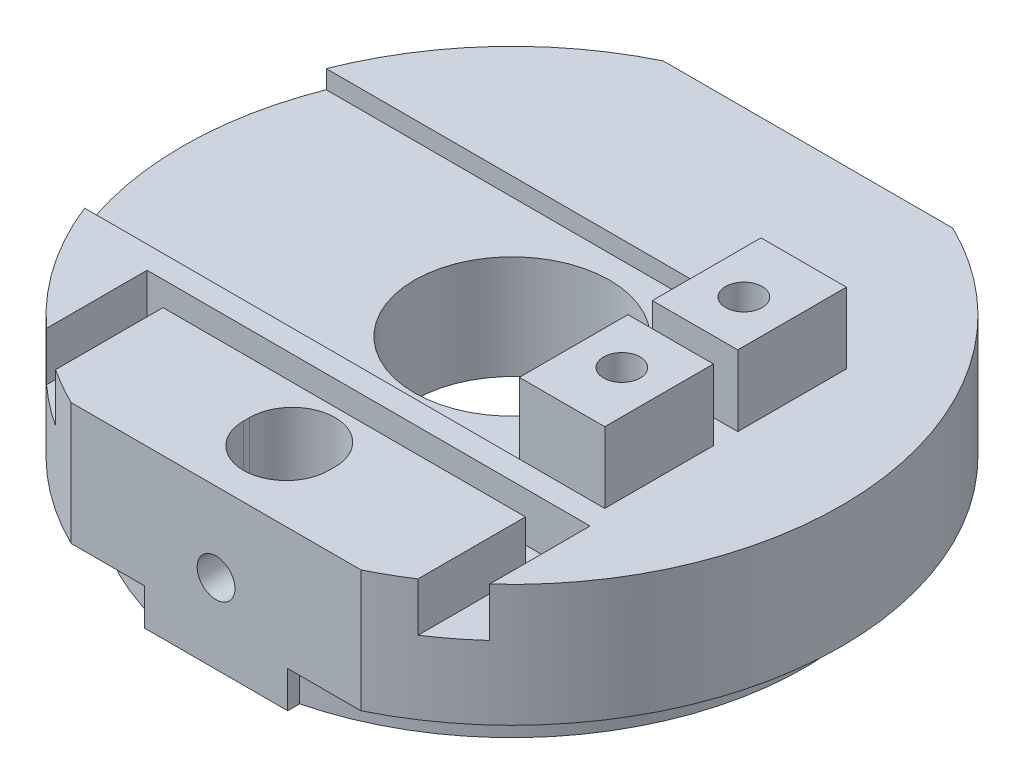
SolidWorks part; units mm, degrees
ref_plane "Front Plane" through (0, 0, 0) normal (0, 0, 1) x (1, 0, 0)
ref_plane "Top Plane" through (0, 0, 0) normal (0, 1, 0) x (1, 0, 0)
ref_plane "Right Plane" through (0, 0, 0) normal (1, 0, 0) x (0, 0, -1)
sketch "Sketch1" plane through (0, 0, 0) normal (0, 1, 0) x (1, 0, 0)
  line L0 (0, -18) -> (0, -18.5) construction
  line L5 (3.5, -18) -> (3.5, -18.5)
  line L6 (-3.5, -18) -> (-3.5, -18.5)
  line L7 (0, -14.5) -> (0, -8) construction
  line L8 (0, 27) -> (0, 24) construction
  line L9 (-17.5, -27) -> (17.5, -27)
  line L10 (-17.5, -27) -> (-17.5, -24.25)
  line L11 (-17.5, -24.25) -> (17.5, -24.25)
  line L12 (17.5, -27) -> (17.5, -24.25)
  line L13 (5.8745, -24.25) -> (-5.8745, -24.25)
  line L14 (5.8745, -24.25) -> (5.8745, -23.2699)
  line L15 (5.8745, -23.2699) -> (-5.8745, -23.2699)
  line L16 (-5.8745, -24.25) -> (-5.8745, -23.2699)
  line L18 (17.5, 27) -> (-17.5, 27)
  line L19 (17.5, 27) -> (17.5, 24.25)
  line L20 (17.5, 24.25) -> (-17.5, 24.25)
  line L21 (-17.5, 27) -> (-17.5, 24.25)
  circle A0 centre (0, 0) radius 8
  circle A1 centre (0, 0) radius 27
  circle A2 centre (0, 0) radius 24
  circle A3 centre (0, 0) radius 22
  arc A4 (3.5, -18) -> (-3.5, -18) centre (0, -18) ccw
  arc A5 (-3.5, -18.5) -> (3.5, -18.5) centre (0, -18.5) ccw
  circle A6 centre (0, 0) radius 20.75 construction
  circle A7 centre (0, 0) radius 14.5 construction
  point P12 (0, -18.25)
  point P17 (0, -14.5)
  point P18 (0, -22)
  point P23 (0, -27)
  point P24 (0, -23.2699)
  point P35 (24.3506, 24)
  dimension "D1" = 16
  dimension "D2" = 54
  dimension "D3" = 48
  dimension "D4" = 44
  dimension "D5" = 3.5
  dimension "D8" = 41.5
  dimension "D9" = 29
  dimension "D6" = 7.5
  dimension "D7" = 6.5
  dimension "D10" = 35
  dimension "D11" = 24.25
  dimension "D12" = 11.749
extrude "Boss-Extrude1" add sketch "Sketch1" along normal blind 10 contours A2 L9 A1 | L9 A2 A3 | A3 A5 L6 A4 L5 A0 | L15 A2 | A2 L16 L11 region at (-15.1163, 0, -15.1163) region at (-26.2742, 0, 0) region at (-5.7566, 0, 23.76) region at (-14.3341, 0, -18.4025) region at (0, 0, 23.5623)
extrude "Boss-Extrude2" add sketch "Sketch1<3>" against normal blind 3 contours L9 A2 A3 | A2 L13 L14 | A2 L15 region at (-5.7566, 0, 23.76) region at (-14.3341, 0, -18.4025) region at (0, 0, 23.5623)
sketch "Sketch1<3>" plane through (0, 0, 0) normal (0, 1, 0) x (1, 0, 0) same geometry as "Sketch1"
sketch "Sketch2" plane through (0, 10, 0) normal (0, 1, 0) x (1, 0, 0)
  line L0 (0, -11.75) -> (0, -14.5) construction
  line L5 (-18.15, -24.25) -> (18.15, -24.25)
  line L6 (-18.15, -24.25) -> (-18.15, -11.75)
  line L7 (-18.15, -11.75) -> (18.15, -11.75)
  line L8 (18.15, -24.25) -> (18.15, -11.75)
  line L10 (-14.85, -24.25) -> (-14.85, -13.75)
  line L11 (-14.85, -13.75) -> (14.85, -13.75)
  line L12 (14.85, -13.75) -> (14.85, -24.25)
  line L13 (-14.85, -13.75) -> (-18.15, -13.75) construction
  line L14 (14.85, -13.75) -> (18.15, -13.75) construction
  line L15 (14.85, -13.75) -> (14.85, -11.75) construction
  line L16 (-11.8717, -24.25) -> (11.8717, -24.25) construction
  line L17 (25.1195, -9.9) -> (-25.1195, -9.9) construction
  arc A0 (3.5, -18) -> (-3.5, -18) centre (0, -18) ccw construction
  arc A1 (11.8717, -24.25) -> (11.8717, 24.25) centre (0, 0) ccw construction
  arc A2 (-11.8717, 24.25) -> (-11.8717, -24.25) centre (0, 0) ccw construction
  point P3 (0, -13.75)
  point P10 (-16.5, -13.75)
  point P21 (16.5, -13.75)
  point P22 (14.85, -12.75)
  dimension "D1" = 3.3
  dimension "D2" = 2
  dimension "D3" = 33
  dimension "D4" = 11.5
  dimension "D5" = 9.9
extrude "Cut-Extrude1" cut sketch "Sketch2" against normal blind 4 contours L11 L12 L8 L7 L6 L10 region at (-17.7661, 10, 18)
sketch "Sketch3" plane through (0, 10, 0) normal (0, 1, 0) x (1, 0, 0)
  line L1 (-27, 9.9) -> (10.5, 9.9)
  line L2 (-27, 9.9) -> (-27, -9.9)
  line L3 (-27, -9.9) -> (10.5, -9.9)
  line L4 (10.5, 9.9) -> (10.5, -9.9)
  arc A0 (18.15, -19.9894) -> (11.8717, 24.25) centre (0, 0) ccw construction
  point P4 (10.5, 0)
  point P6 (-31.8808, -9.9)
  dimension "D1" = 19.8
  dimension "D2" = 10.5
extrude "Cut-Extrude2" cut sketch "Sketch3" against normal blind 1.5
sketch "Sketch4" plane through (0, 10, 0) normal (0, 1, 0) x (1, 0, 0)
  line L0 (14, 5) -> (14, -5) construction
  line L1 (10.5, 9.9) -> (17.5, 9.9)
  line L2 (10.5, 9.9) -> (10.5, 1)
  line L3 (10.5, 1) -> (17.5, 1)
  line L4 (17.5, 9.9) -> (17.5, 1)
  line L5 (10.5, -9.9) -> (17.5, -9.9)
  line L6 (10.5, -9.9) -> (10.5, -1)
  line L7 (10.5, -1) -> (17.5, -1)
  line L8 (17.5, -9.9) -> (17.5, -1)
  line L9 (10.5, -9.9) -> (10.5, 9.9) construction
  line L10 (10.5, -9.9) -> (10.5, 9.9) construction
  circle A0 centre (14, 5) radius 1.5
  circle A1 centre (14, -5) radius 1.5
  point P9 (10.5, -9.9)
  point P14 (14, 0)
  point P15 (10.5, -9.4)
  point P16 (14, -9.9)
  point P20 (10.5, 0)
  point P21 (15.4254, 5.075)
  point P22 (10.5, -7.9101)
  dimension "D2" = 10
  dimension "D3" = 3
  dimension "D1" = 2
  dimension "D4" = 3.5
extrude "Boss-Extrude3" add sketch "Sketch4" along normal blind 5.8
sketch "Sketch5" plane through (0, 0, 24.25) normal (0, 0, 1) x (1, 0, 0)
  line L0 (18.15, 6) -> (14.85, 6) construction
  circle A0 centre (0, 3.5) radius 1.55
  point P2 (0, 0)
  point P4 (13.5, 3.6798)
  dimension "D1" = 3.1
  dimension "D2" = 2.5
extrude "Cut-Extrude3" cut sketch "Sketch5" against normal blind 6
